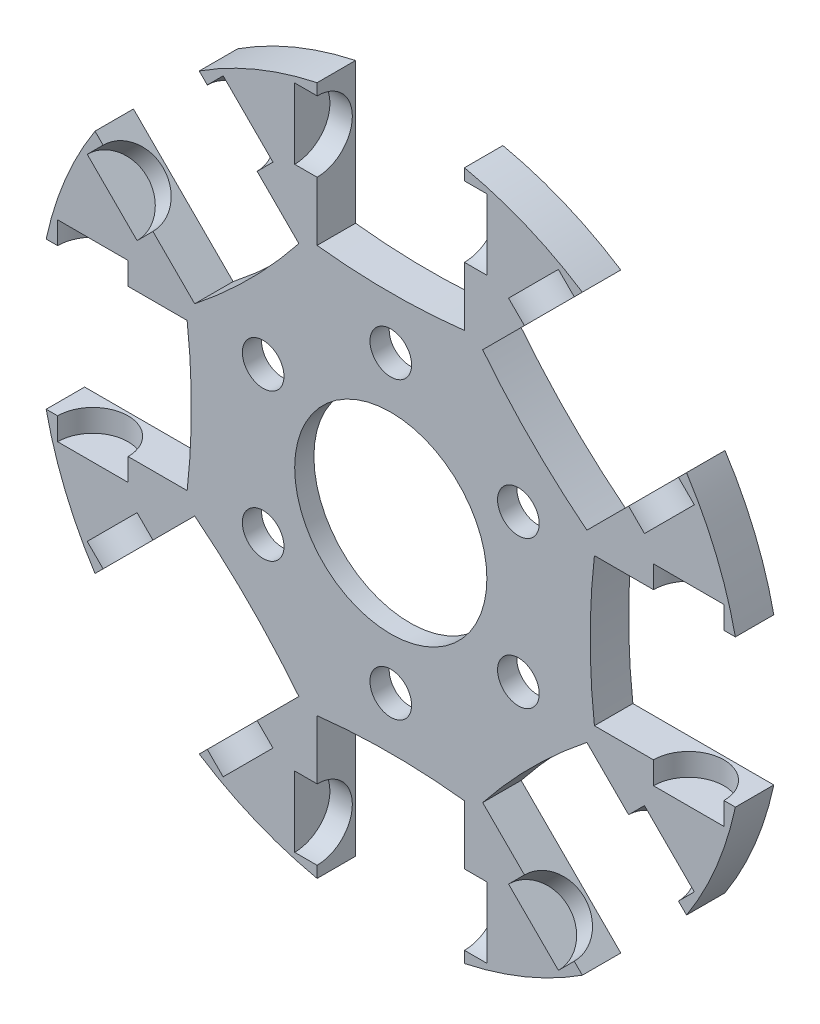
SolidWorks part; units mm, degrees
ref_plane "Front Plane" through (0, 0, 0) normal (0, 0, 1) x (1, 0, 0)
ref_plane "Top Plane" through (0, 0, 0) normal (0, 1, 0) x (1, 0, 0)
ref_plane "Right Plane" through (0, 0, 0) normal (1, 0, 0) x (0, 0, -1)
sketch "Sketch2" plane through (0, 0, 0) normal (0, 0, 1) x (1, 0, 0)
  line L0 (0, -2.3056) -> (0, 37.2834) construction
  line L1 (-5.75, 28.5556) -> (5.75, 28.5556) construction
  line L2 (-5.75, 26.8921) -> (-5.75, 15.8921)
  line L3 (5.75, 26.8921) -> (5.75, 15.8921)
  line L4 (14.9498, 23.0815) -> (7.1716, 15.3033)
  line L5 (23.0815, 14.9498) -> (15.3033, 7.1716)
  line L6 (26.8921, 5.75) -> (15.8921, 5.75)
  line L7 (26.8921, -5.75) -> (15.8921, -5.75)
  line L8 (23.0815, -14.9498) -> (15.3033, -7.1716)
  line L9 (14.9498, -23.0815) -> (7.1716, -15.3033)
  line L10 (5.75, -26.8921) -> (5.75, -15.8921)
  line L11 (-5.75, -26.8921) -> (-5.75, -15.8921)
  line L12 (-14.9498, -23.0815) -> (-7.1716, -15.3033)
  line L13 (-23.0815, -14.9498) -> (-15.3033, -7.1716)
  line L14 (-26.8921, -5.75) -> (-15.8921, -5.75)
  line L15 (-26.8921, 5.75) -> (-15.8921, 5.75)
  line L16 (-23.0815, 14.9498) -> (-15.3033, 7.1716)
  line L17 (-14.9498, 23.0815) -> (-7.1716, 15.3033)
  circle A0 centre (0, 0) radius 27.5
  circle A1 centre (0, 0) radius 11.5 construction
  circle A2 centre (0, 0) radius 14 construction
  circle A3 centre (-9.9593, 5.75) radius 1.625
  circle A4 centre (0, 11.5) radius 1.625
  circle A5 centre (9.9593, 5.75) radius 1.625
  circle A6 centre (9.9593, -5.75) radius 1.625
  circle A7 centre (0, -11.5) radius 1.625
  circle A8 centre (-9.9593, -5.75) radius 1.625
  arc A9 (-5.75, 15.8921) -> (5.75, 15.8921) centre (0, 65.5604) ccw
  arc A10 (7.1716, 15.3033) -> (15.3033, 7.1716) centre (46.3582, 46.3582) ccw
  arc A11 (15.8921, 5.75) -> (15.8921, -5.75) centre (65.5604, 0) ccw
  arc A12 (15.3033, -7.1716) -> (7.1716, -15.3033) centre (46.3582, -46.3582) ccw
  arc A13 (5.75, -15.8921) -> (-5.75, -15.8921) centre (0, -65.5604) ccw
  arc A14 (-7.1716, -15.3033) -> (-15.3033, -7.1716) centre (-46.3582, -46.3582) ccw
  arc A15 (-15.8921, -5.75) -> (-15.8921, 5.75) centre (-65.5604, 0) ccw
  arc A16 (-15.3033, 7.1716) -> (-7.1716, 15.3033) centre (-46.3582, 46.3582) ccw
  circle A19 centre (0, 0) radius 7.5
  circle A20 centre (0, 0) radius 14
  point P9 (0, 28.5556)
  point P25 (0, 0)
  point P67 (1.5089, -0.625)
  point P69 (0, 0)
  point P75 (0, 0)
  point P79 (0, 0)
  point P80 (0, 0)
  point P81 (0, 0)
  point P83 (-22.6761, 7.3679)
  dimension "D1" = 55
  dimension "D2" = 11.5
  dimension "37" = 23
  dimension "D3" = 8
  dimension "35" = 28
  dimension "D4" = 3.25
  dimension "D8" = 15
  dimension "D7" = 50
  dimension "D6" = 11
  dimension "D5" = 6
extrude "Boss-Extrude2" add sketch "Sketch2" along normal blind 3 contours A0 L3 A9 L2 A20 | A20 A3 A4 A5 A6 A7 A8 A19 region at (-6.5106, 21.3921, 0) region at (-13.604, 0, 0)
extrude "Boss-Extrude3" add sketch "Sketch2<4>" along normal blind 3 contours A20 A8 A1 A3 A4 A5 A6 A7 region at (-13.604, 0, 0)
sketch "Sketch2<4>" plane through (0, 0, 0) normal (0, 0, 1) x (1, 0, 0) same geometry as "Sketch2"
sketch "Sketch3" plane through (0, 0, 3) normal (0, 0, 1) x (1, 0, 0)
  line L0 (0, 28.1882) -> (0, 8.7236) construction
  line L1 (-4.625, 27.1083) -> (4.625, 27.1083) construction
  line L3 (-6.683, 23) -> (6.8867, 23) construction
  line L4 (-7.5, 26) -> (7.5, 26)
  line L5 (7.5, 26) -> (7.5, 23.25)
  line L6 (-7.5, 26) -> (-7.5, 23.25)
  line L7 (7.5, 23.25) -> (-7.5, 23.25)
  point P15 (0, 26)
  dimension "D1" = 23
  dimension "D2" = 15
  dimension "D3" = 3
  dimension "D4" = 2.75
revolve "Cut-Revolve1" cut sketch "Sketch3" angle 360 about L7
sketch "Sketch5" plane through (0, 0, 0) normal (0, 0, -1) x (-1, 0, 0)
  circle A0 centre (0, 0) radius 15.5
  dimension "D1" = 31
extrude "Cut-Extrude2" cut sketch "Sketch5" against normal blind 1.5
pattern_circular "CirPattern2" count 8 over 360 about axis through (0, 0, 3) along (0, 0, 1) of "Cut-Revolve1"
